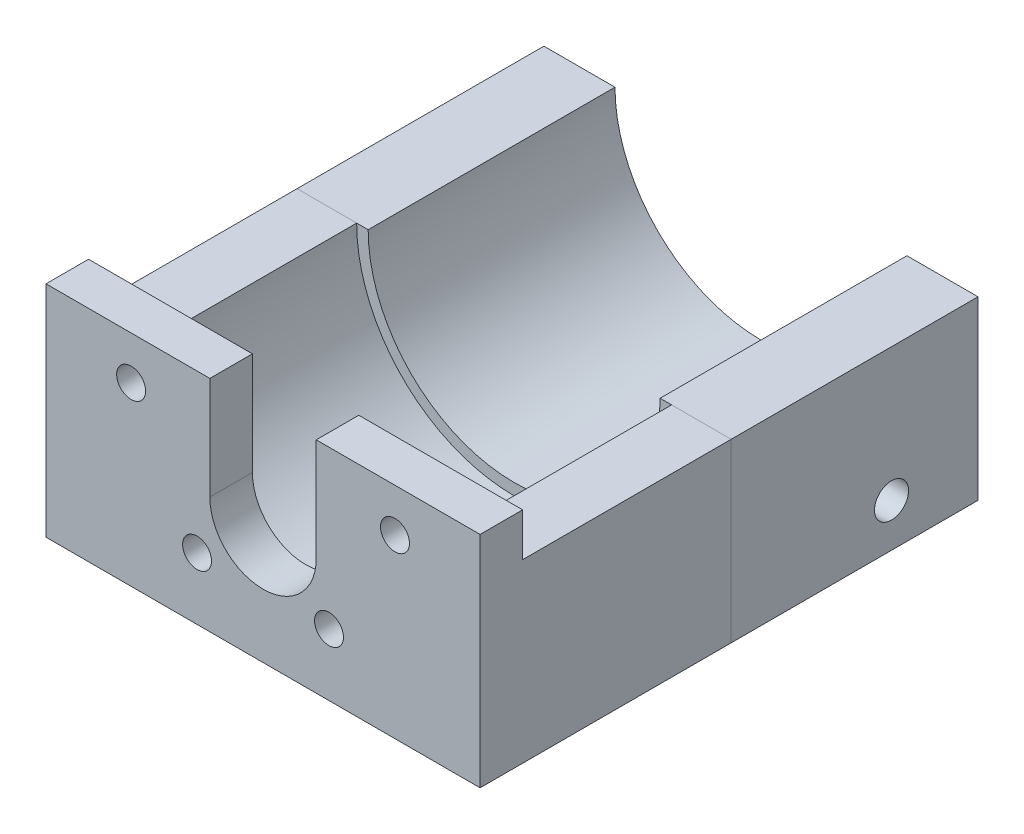
SolidWorks part; units mm, degrees
ref_plane "Front Plane" through (0, 0, 0) normal (0, 0, 1) x (1, 0, 0)
ref_plane "Top Plane" through (0, 0, 0) normal (0, 1, 0) x (1, 0, 0)
ref_plane "Right Plane" through (0, 0, 0) normal (1, 0, 0) x (0, 0, -1)
sketch "Sketch1" plane through (0, 0, 0) normal (0, 0, 1) x (1, 0, 0)
  line L0 (18.5, 0) -> (25.5, 0)
  line L1 (25.5, 0) -> (25.5, -20.716)
  line L2 (25.5, -20.716) -> (-25.5, -20.716)
  line L3 (-25.5, -20.716) -> (-25.5, 0)
  line L4 (-25.5, 0) -> (-18.5, 0)
  arc A0 (-18.5, 0) -> (18.5, 0) centre (0, 0) ccw
  dimension "D1" = 37
  dimension "D2" = 7
  dimension "D3" = 7
  dimension "D4" = 20.716
extrude "Boss-Extrude1" add sketch "Sketch1" along normal blind 24.5
sketch "Sketch2" plane through (0, 0, 24.5) normal (0, 0, 1) x (1, 0, 0)
  line L0 (-25.5, -20.716) -> (25.5, -20.716)
  line L2 (-25.5, -20.716) -> (-25.5, 5.071)
  line L5 (25.5, -20.716) -> (25.5, 5.071)
  line L6 (25.5, 5.071) -> (6.25, 5.071)
  line L7 (6.25, -7) -> (6.25, 5.071)
  line L8 (-6.25, -7) -> (-6.25, 5.071)
  line L9 (-6.25, 5.071) -> (-25.5, 5.071)
  arc A0 (-6.25, -7) -> (6.25, -7) centre (0, -7) ccw
  circle A1 centre (15.5, 0) radius 1.7
  circle A2 centre (-7.75, -13.4234) radius 1.7
  circle A4 centre (-15.5, 0) radius 1.7
  circle A6 centre (7.75, -13.4234) radius 1.7
  circle A7 centre (7.75, 13.4234) radius 1.7 [skipped]
  circle A8 centre (-7.75, 13.4234) radius 1.7 [skipped]
  point P17 (0, 0)
  point P24 (0, 0)
  dimension "D4" = 12.5
  dimension "D6" = 3.4
  dimension "D9" = 3.4
  dimension "D3" = 7
  dimension "D5" = 15.5
  dimension "D8" = 15.5
  dimension "D7" = 3
  dimension "D10" = 3
extrude "Boss-Extrude2" add sketch "Sketch2" along normal blind 5
sketch "Sketch3" plane through (0, 0, 0) normal (0, 0, -1) x (-1, 0, 0)
  line L0 (17.15, 0) -> (25.5, 0)
  line L1 (25.5, 0) -> (25.5, -20.716)
  line L2 (25.5, -20.716) -> (-25.5, -20.716)
  line L3 (-25.5, -20.716) -> (-25.5, 0)
  line L4 (-25.5, 0) -> (-17.15, 0)
  arc A0 (-17.15, 0) -> (17.15, 0) centre (0, 0) ccw
  dimension "D1" = 34.3
  dimension "D2" = 8.35
extrude "Boss-Extrude3" add sketch "Sketch3" along normal blind 29
sketch "Sketch4" plane through (0, -20.716, 0) normal (0, -1, 0) x (1, 0, 0)
  line L0 (-25.5, 29.5) -> (25.5, 29.5) construction
  line L1 (-25.5, 29.5) -> (-25.5, 0) construction
  line L2 (25.5, 29.5) -> (25.5, 0) construction
  line L3 (25.5, -29) -> (-25.5, -29) construction
  circle A0 centre (-21.69, 25.69) radius 2
  circle A1 centre (21.69, 25.69) radius 2
  circle A2 centre (-21.69, -25.19) radius 2
  circle A3 centre (21.69, -25.19) radius 2
  dimension "D1" = 4
  dimension "D2" = 4
  dimension "D3" = 4
  dimension "D4" = 4
  dimension "D5" = 3.81
  dimension "D6" = 3.81
  dimension "D7" = 3.81
  dimension "D9" = 3.81
  dimension "D10" = 3.81
  dimension "D11" = 3.81
  dimension "D12" = 3.81
  dimension "D13" = 43.38
  dimension "D14" = 50.88
  dimension "D8" = 3.81
extrude "Cut-Extrude1" cut sketch "Sketch4" against normal blind 7
sketch "Sketch5" plane through (-25.5, 0, 0) normal (-1, 0, 0) x (0, 0, 1)
  line L0 (29.5, -20.716) -> (0, -20.716) construction
  line L1 (-29, -20.716) -> (-29, 0) construction
  circle A0 centre (-18.84, -15.636) radius 2
  dimension "D1" = 4
  dimension "D3" = 10.16
  dimension "D2" = 5.08
sketch "Sketch6" plane through (25.5, 0, 0) normal (1, 0, 0) x (0, 0, -1)
  line L1 (-24.5, 0) -> (0, 0) construction
  circle A0 centre (18.84, -15.636) radius 2
  dimension "D1" = 4
  dimension "D2" = 15.636
extrude "Cut-Extrude2" cut sketch "Sketch5" against normal blind 7
extrude "Cut-Extrude3" cut sketch "Sketch6" against normal blind 7
